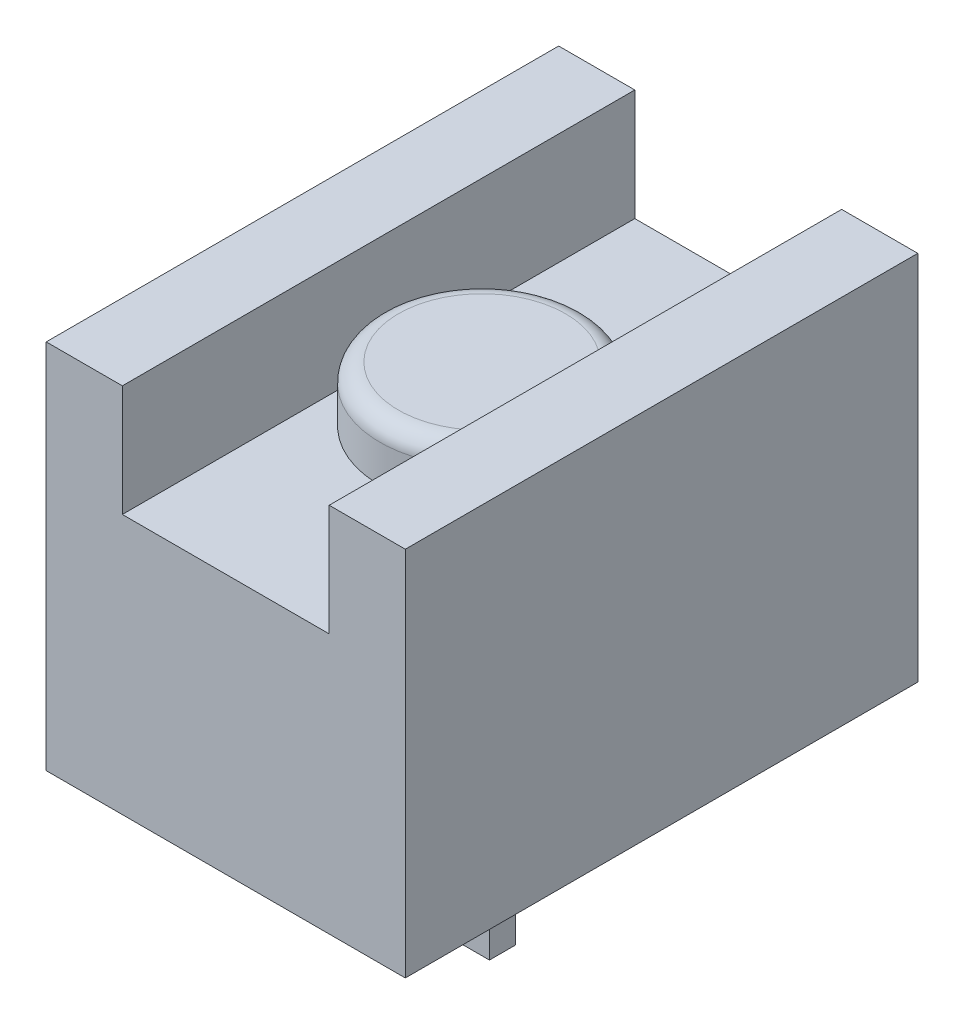
SolidWorks part; units mm, degrees
ref_plane "前视基准面" through (0, 0, 0) normal (0, 0, 1) x (1, 0, 0)
ref_plane "上视基准面" through (0, 0, 0) normal (0, 1, 0) x (1, 0, 0)
ref_plane "右视基准面" through (0, 0, 0) normal (1, 0, 0) x (0, 0, -1)
sketch "草图1" plane through (0, 0, 0) normal (0, 1, 0) x (1, 0, 0)
  line L0 (-11.1447, 0) -> (12.1543, 0) construction
  line L1 (-4.835, 6.9) -> (4.835, 6.9)
  line L2 (-4.835, 6.9) -> (-4.835, -6.9)
  line L3 (-4.835, -6.9) -> (4.835, -6.9)
  line L4 (4.835, 6.9) -> (4.835, -6.9)
  line L5 (0, 11.4931) -> (0, -8.9219) construction
  dimension "D1" = 9.67
  dimension "D2" = 13.8
extrude "拉伸1" add sketch "草图1" along normal blind 10
sketch "草图2" plane through (0, 10, 0) normal (0, 1, 0) x (-1, 0, 0)
  line L0 (4.835, 6.9) -> (-4.835, 6.9) construction
  line L1 (-2.785, 6.9) -> (2.785, 6.9)
  line L3 (-2.785, 6.9) -> (-2.785, -6.9)
  line L4 (-2.785, -6.9) -> (2.785, -6.9)
  line L5 (2.785, 6.9) -> (2.785, -6.9)
  line L6 (-4.835, -6.9) -> (4.835, -6.9) construction
  line L7 (-4.835, 6.9) -> (-4.835, -6.9) construction
  line L10 (4.835, -6.9) -> (4.835, 6.9) construction
  dimension "D1" = 2.05
  dimension "D2" = 2.05
extrude "切除-拉伸1" cut sketch "草图2" against normal blind 3
sketch "草图3" plane through (0, 0, 0) normal (0, -1, 0) x (1, 0, 0)
  line L0 (-1.1261, 0) -> (1.1036, 0) construction
  line L1 (-0.55, 0.35) -> (0.55, 0.35)
  line L2 (-0.55, 0.35) -> (-0.55, -0.35)
  line L3 (-0.55, -0.35) -> (0.55, -0.35)
  line L4 (0.55, 0.35) -> (0.55, -0.35)
  line L5 (0, 0.8666) -> (0, -0.8367) construction
  dimension "D2" = 0.7
  dimension "D1" = 1.1
extrude "拉伸2" add sketch "草图3" along normal blind 5
sketch "草图4" plane through (0, 7, 0) normal (0, 1, 0) x (-1, 0, 0)
  line L0 (-9.5136, 0) -> (8.6579, 0) construction
  line L1 (0, -7.7686) -> (0, 8.3952) construction
  circle A1 centre (0, 0) radius 2.75
  dimension "D1" = 5.5
extrude "凸台-拉伸1" add sketch "草图4" along normal blind 1.5
fillet "圆角1" radius 0.5 1 edges at (0, 8.5, -2.75)
